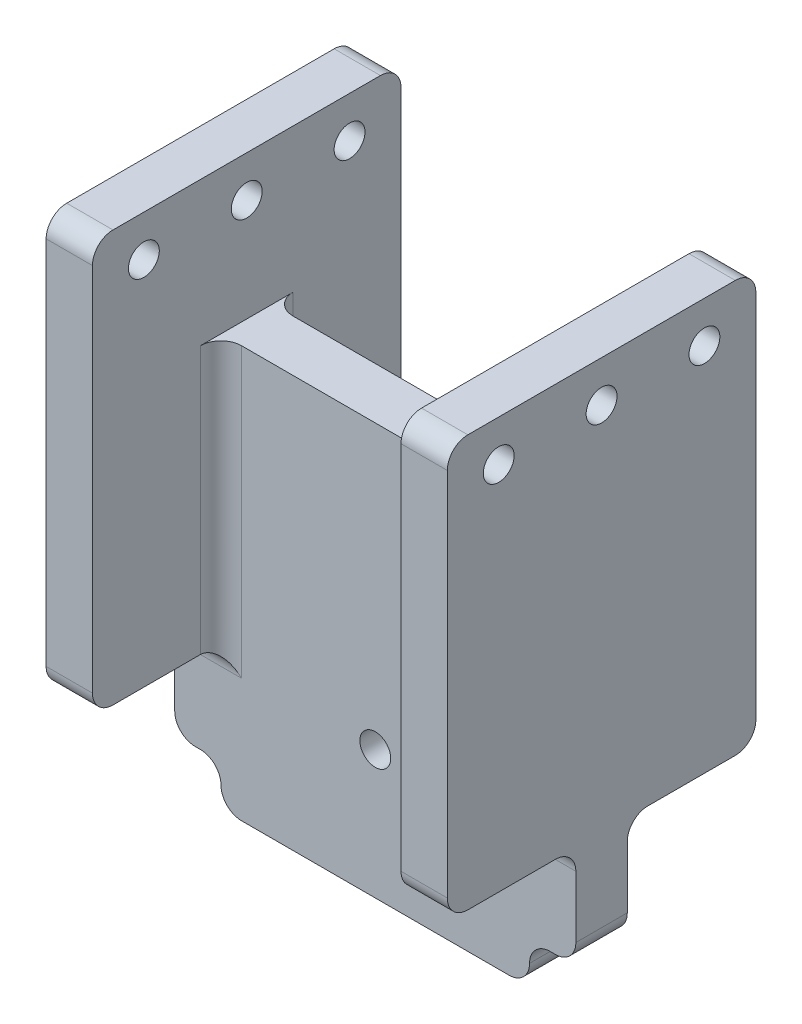
SolidWorks part; units mm, degrees
ref_plane "前视基准面" through (0, 0, 0) normal (0, 0, 1) x (1, 0, 0)
ref_plane "上视基准面" through (0, 0, 0) normal (0, 1, 0) x (1, 0, 0)
ref_plane "右视基准面" through (0, 0, 0) normal (1, 0, 0) x (0, 0, -1)
sketch "草图1" plane through (0, 0, 0) normal (0, 0, 1) x (1, 0, 0)
  line L1 (15, -25) -> (-15, -25)
  line L2 (15, -25) -> (15, 25)
  line L3 (15, 25) -> (-15, 25)
  line L4 (-15, -25) -> (-15, 25)
  line L5 (15, -25) -> (-15, 25) construction
  line L6 (15, 25) -> (-15, -25) construction
  point P0 (0, 0)
  dimension "D1" = 30
  dimension "D2" = 50
extrude "凸台-拉伸1" add sketch "草图1" along normal blind 5
sketch "草图5" plane through (-15, 0, 0) normal (-1, 0, 0) x (0, 0, 1)
  line L0 (5, 25) -> (0, 25) construction
  line L1 (17.5, 9) -> (-12.5, 9)
  line L2 (17.5, 9) -> (17.5, 59)
  line L3 (17.5, 59) -> (-12.5, 59)
  line L4 (-12.5, 9) -> (-12.5, 59)
  line L5 (17.5, 9) -> (-12.5, 59) construction
  line L6 (17.5, 59) -> (-12.5, 9) construction
  line L7 (2.5, -25) -> (2.5, 25) construction
  line L8 (5, -25) -> (0, -25) construction
  line L9 (2.5, 25) -> (2.5, 40.0267) construction
  point P0 (2.5, 34)
  dimension "D1" = 16
  dimension "D2" = 30
  dimension "D3" = 50
extrude "凸台-拉伸2" add sketch "草图5" along normal blind 4.5
mirror "镜向1" about plane through (0, 0, 0) normal (1, 0, 0) of "凸台-拉伸2"
sketch "草图6" plane through (-19.5, 0, 0) normal (-1, 0, 0) x (0, 0, 1)
  line L0 (2.5, 59) -> (2.5, 55) construction
  line L1 (17.5, 59) -> (-12.5, 59) construction
  circle A0 centre (2.5, 55) radius 1.5
  dimension "D1" = 4
  dimension "D2" = 3
extrude "切除-拉伸1" cut sketch "草图6" against normal through all
sketch "草图7" plane through (-19.5, 0, 0) normal (-1, 0, 0) x (0, 0, 1)
  line L0 (2.5, 55) -> (-7.5, 55) construction
  line L1 (2.5, 55) -> (12.5, 55) construction
  circle A0 centre (-7.5, 55) radius 1.5
  circle A1 centre (12.5, 55) radius 1.5
  dimension "D3" = 3
  dimension "D4" = 3
  dimension "D1" = 10
  dimension "D2" = 10
extrude "切除-拉伸2" cut sketch "草图7" against normal through all
sketch "草图9" plane through (0, 0, 5) normal (0, 0, 1) x (1, 0, 0)
  line L0 (0, -25) -> (0, -19) construction
  line L1 (-15, -25) -> (15, -25) construction
  circle A0 centre (0, -19) radius 1.5
  dimension "D2" = 3
  dimension "D1" = 6
sketch "草图10" plane through (0, 0, 0) normal (0, 0, -1) x (-1, 0, 0)
  line L0 (0, 1.5) -> (0, 12.5) construction
  circle A0 centre (0, 1.5) radius 1.5
  circle A1 centre (0, 12.5) radius 1.5
  dimension "D1" = 3
  dimension "D2" = 3
  dimension "D3" = 11
sketch "草图11" plane through (0, 0, 0) normal (0, 0, -1) x (-1, 0, 0)
  line L0 (-15, -25) -> (-15, 9) construction
  line L1 (15, -25) -> (-15, -25)
  line L2 (15, -25) -> (15, 3)
  line L3 (15, 3) -> (-15, 3)
  line L4 (-15, -25) -> (-15, 3)
  dimension "D1" = 28
sketch "草图12" plane through (-15, 0, 0) normal (1, 0, 0) x (0, 0, -1)
  line L0 (12.5, 59) -> (12.5, 9) construction
  line L1 (0, 9) -> (12.5, 9)
  line L2 (0, 9) -> (0, 19)
  line L3 (0, 19) -> (12.5, 19)
  line L4 (12.5, 9) -> (12.5, 19)
  line L5 (-17.5, 9) -> (-17.5, 59) construction
  line L6 (-5, 9) -> (-17.5, 9)
  line L7 (-5, 9) -> (-5, 19)
  line L8 (-5, 19) -> (-17.5, 19)
  line L9 (-17.5, 9) -> (-17.5, 19)
  dimension "D1" = 10
  dimension "D2" = 10
sketch "草图13" plane through (15, 0, 0) normal (-1, 0, 0) x (0, 0, 1)
  line L0 (17.5, 9) -> (17.5, 59) construction
  line L1 (5, 9) -> (17.5, 9)
  line L2 (5, 9) -> (5, 19)
  line L3 (5, 19) -> (17.5, 19)
  line L4 (17.5, 9) -> (17.5, 19)
  line L5 (-12.5, 59) -> (-12.5, 9) construction
  line L6 (0, 9) -> (-12.5, 9)
  line L7 (0, 9) -> (0, 19)
  line L8 (0, 19) -> (-12.5, 19)
  line L9 (-12.5, 9) -> (-12.5, 19)
  dimension "D1" = 10
  dimension "D2" = 10
sketch "草图14" plane through (0, 0, 0) normal (0, 0, -1) x (-1, 0, 0)
  line L1 (-15, -25) -> (23.6948, -25)
  line L2 (-15, -25) -> (-15, -7)
  line L3 (-15, -7) -> (23.6948, -7)
  line L4 (23.6948, -25) -> (23.6948, -7)
  dimension "D1" = 18
extrude "切除-拉伸8" cut sketch "草图12" against normal through all
extrude "切除-拉伸9" cut sketch "草图13" against normal through all
sketch "草图15" plane through (0, 0, 5) normal (0, 0, 1) x (1, 0, 0)
  circle A0 centre (0, 1.5) radius 1.25
sketch "草图16" plane through (0, 25, 0) normal (0, 1, 0) x (1, 0, 0)
  line L4 (15, 0) -> (-15, 0)
  line L5 (-15, 0) -> (-15, -5)
  line L6 (-15, -5) -> (15, -5)
  line L7 (15, -5) -> (15, 0)
  line L8 (15, 0) -> (-15, 0)
  line L9 (-15, 0) -> (-15, -5)
  line L10 (-15, -5) -> (15, -5)
  line L11 (15, -5) -> (15, 0)
  dimension "D1" = 0
extrude "凸台-拉伸3" add sketch "草图16" along normal blind 20
sketch "草图17" plane through (0, 0, 5) normal (0, 0, 1) x (1, 0, 0)
  line L0 (0, 1.5) -> (0, 12.5) construction
  circle A0 centre (0, 12.5) radius 1.5
  dimension "D1" = 3
  dimension "D2" = 11
extrude "切除-拉伸10" cut sketch "草图17" against normal blind 20
sketch "草图18" plane through (0, 0, 5) normal (0, 0, 1) x (1, 0, 0)
  line L0 (-19.5, 9) -> (-15, 9) construction
  line L1 (-20.7485, 5) -> (32.37, 5)
  line L2 (-20.7485, 5) -> (-20.7485, -43.9882)
  line L3 (-20.7485, -43.9882) -> (32.37, -43.9882)
  line L4 (32.37, 5) -> (32.37, -43.9882)
  dimension "D1" = 4
extrude "切除-拉伸11" cut sketch "草图18" against normal blind 20
fillet "圆角1" radius 2 4 edges at (-17.25, 19, 0) (17.25, 19, 0) (17.25, 19, 5) (-17.25, 19, 5)
fillet "圆角2" radius 2 4 edges at (15, 31, 0) (-15, 31, 0) (15, 31, 5) (-15, 31, 5)
fillet "圆角3" radius 2 8 edges at (-17.25, 19, 17.5) (17.25, 19, 17.5) (17.25, 59, 17.5) (-17.25, 59, 17.5) (-17.25, 59, -12.5) (17.25, 59, -12.5) (-17.25, 19, -12.5) (17.25, 19, -12.5)
fillet "圆角4" radius 2 6 edges at (15, 9, 2.5) (-15, 9, 2.5) (19.5, 9, 2.5) (15, 5, 2.5) (-15, 5, 2.5) (-19.5, 9, 2.5)
sketch "草图19" plane through (0, 0, 5) normal (0, 0, 1) x (1, 0, 0)
  line L0 (0, 12.5) -> (0, 17.5) construction
  circle A0 centre (0, 17.5) radius 1.5
  dimension "D1" = 3
  dimension "D2" = 5
extrude "切除-拉伸12" cut sketch "草图19" against normal blind 10
sketch "草图21" plane through (0, 0, 5) normal (0, 0, 1) x (1, 0, 0)
  circle A0 centre (0, 12.5) radius 1.5 construction
  circle A1 centre (0, 12.5) radius 1.5
extrude "凸台-拉伸4" add sketch "草图21" against normal up to surface (5 mm away) up to face at (1.5, 17.5, 0)
